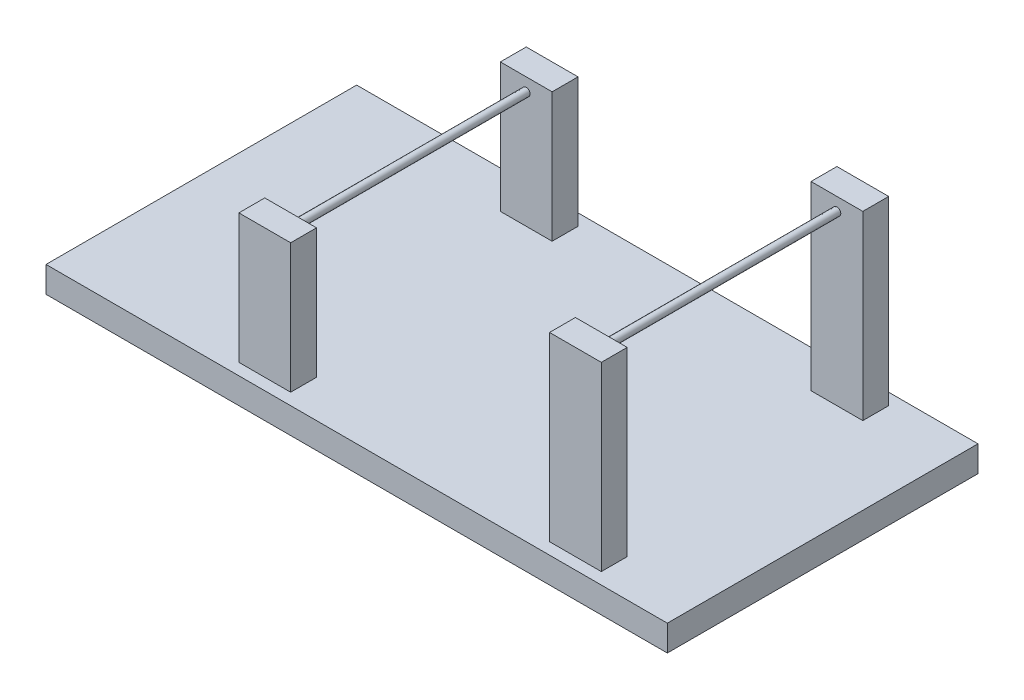
SolidWorks part; units mm, degrees
material "Cedro"
ref_plane "Alzado" through (0, 0, 0) normal (0, 0, 1) x (1, 0, 0)
ref_plane "Planta" through (0, 0, 0) normal (0, 1, 0) x (1, 0, 0)
ref_plane "Vista lateral" through (0, 0, 0) normal (1, 0, 0) x (0, 0, -1)
sketch "Croquis1" plane through (0, 0, 0) normal (0, 1, 0) x (1, 0, 0)
  line L1 (-120, -60) -> (120, -60)
  line L2 (-120, -60) -> (-120, 60)
  line L3 (-120, 60) -> (120, 60)
  line L4 (120, -60) -> (120, 60)
  line L5 (-120, -60) -> (120, 60) construction
  line L6 (-120, 60) -> (120, -60) construction
  point P0 (0, 0)
  dimension "D1" = 240
  dimension "D2" = 120
extrude "Saliente-Extruir1" add sketch "Croquis1" along normal blind 10
sketch "Croquis2" plane through (0, 10, 0) normal (0, 1, 0) x (1, 0, 0)
  line L0 (-120, 0) -> (120, 0) construction
  line L1 (-120, 60) -> (-120, -60) construction
  line L2 (120, -60) -> (120, 60) construction
  line L3 (0, 60) -> (0, -60) construction
  line L4 (120, 60) -> (-120, 60) construction
  line L5 (-120, -60) -> (120, -60) construction
  line L6 (-120, -45.5) -> (120, -45.5) construction
  line L7 (-120, 45.5) -> (120, 45.5) construction
  line L9 (70, 45.5) -> (70, 55.5)
  line L10 (70, -45.5) -> (90, -45.5)
  line L11 (90, -45.5) -> (90, -55.5)
  line L12 (-50, 45.5) -> (-30, 45.5)
  line L13 (-50, 60) -> (-50, -60) construction
  line L14 (-50, 45.5) -> (-50, 55.5)
  line L15 (-50, 55.5) -> (-30, 55.5)
  line L16 (-30, 45.5) -> (-30, 55.5)
  line L17 (70, 45.5) -> (90, 45.5)
  line L18 (70, 55.5) -> (90, 55.5)
  line L19 (90, 45.5) -> (90, 55.5)
  line L20 (70, -55.5) -> (90, -55.5)
  line L21 (70, -45.5) -> (70, -55.5)
  line L22 (-50, -55.5) -> (-30, -55.5)
  line L23 (-30, -45.5) -> (-30, -55.5)
  line L24 (-50, -45.5) -> (-30, -45.5)
  line L25 (-50, -45.5) -> (-50, -55.5)
  dimension "D2" = 20
  dimension "D3" = 10
  dimension "D4" = 100
extrude "Saliente-Extruir2" add sketch "Croquis2" along normal blind 50 contours L14 L12 L16 L15 | L22 L23 L24 L25
extrude "Saliente-Extruir3" add sketch "Croquis2<3>" along normal blind 70 contours L17 L19 L18 L9 | L10 L21 L20 L11 region at (80, 10, -50.5) region at (80, 10, 50.5)
sketch "Croquis2<3>" plane through (0, 10, 0) normal (0, 1, 0) x (1, 0, 0) same geometry as "Croquis2"
sketch "Croquis3" plane through (0, 0, 55.5) normal (0, 0, 1) x (1, 0, 0)
  line L0 (-120, 10) -> (120, 10) construction
  line L1 (-50, 60) -> (-30, 60)
  line L2 (-50, 60) -> (-50, 10)
  line L3 (-50, 10) -> (-30, 10)
  line L4 (-30, 60) -> (-30, 10)
  line L5 (-50, 10) -> (-30, 10) construction
  line L7 (70, 80) -> (90, 80)
  line L8 (70, 80) -> (70, 10)
  line L9 (70, 10) -> (90, 10)
  line L10 (90, 80) -> (90, 10)
  circle A0 centre (-40, 55) radius 1.5
  circle A1 centre (80, 75) radius 1.5
  dimension "D1" = 3
  dimension "D2" = 10
  dimension "D3" = 10
  dimension "D4" = 5
  dimension "D5" = 5
extrude "Saliente-Extruir4" add sketch "Croquis3" against normal up to surface (111 mm away) contours A0 | A1 region at (-40, 55, 55.5) region at (80, 75, 55.5) up to face at (-40, 35, -55.5)
